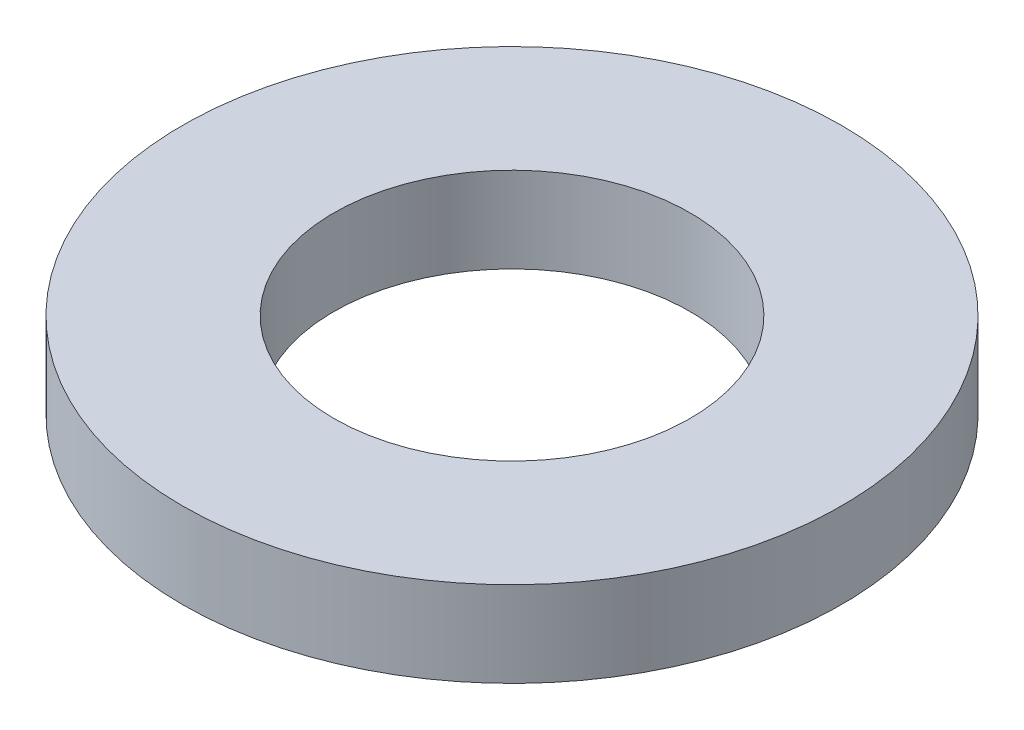
SolidWorks part; units mm, degrees
ref_plane "Front Plane" through (0, 0, 0) normal (0, 0, 1) x (1, 0, 0)
ref_plane "Top Plane" through (0, 0, 0) normal (0, 1, 0) x (1, 0, 0)
ref_plane "Right Plane" through (0, 0, 0) normal (1, 0, 0) x (0, 0, -1)
sketch "Sketch1" plane through (0, 0, 0) normal (0, 1, 0) x (1, 0, 0)
  circle A0 centre (0, 0) radius 92.5
  dimension "FLANGE_OD" = 185
extrude "Boss-Extrude1" add sketch "Sketch1" along normal blind 24
sketch "Sketch2" plane through (0, 0, 0) normal (0, 1, 0) x (1, 0, 0)
  circle A0 centre (0, 0) radius 50
  dimension "BORE_D" = 100
extrude "Cut-Extrude1" cut sketch "Sketch2" along normal through all
sketch "Sketch3" plane through (0, 24, 0) normal (0, 1, 0) x (1, 0, 0)
  circle A0 centre (0, 0) radius 43.6131 construction
  circle A1 centre (-43.6131, 0) radius 3.0651
  dimension "BOLT_D" = 6.1302
  dimension "BOLT_PCD" = 87.2261
extrude "Cut-Extrude2" cut sketch "Sketch3" against normal blind 20.8266 rebuild error yes
pattern_circular "CirPattern1" count 3 over 360 rebuild error yes
